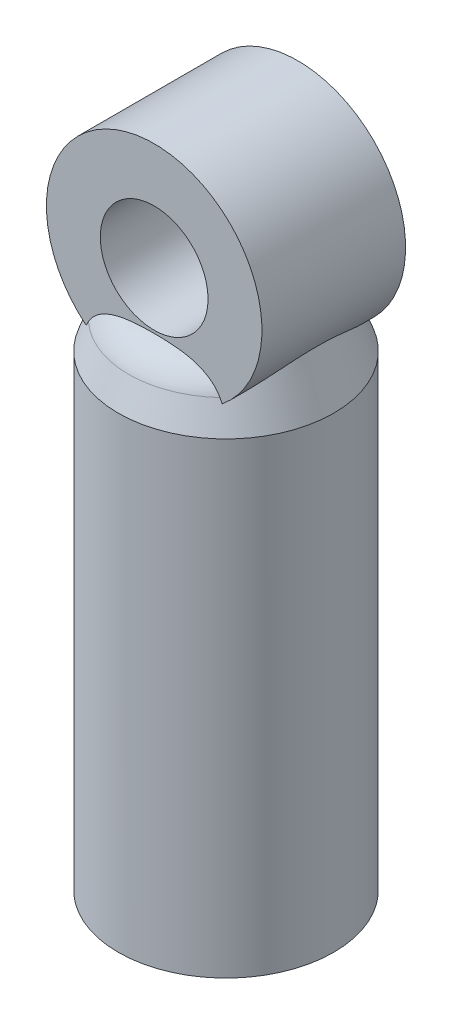
SolidWorks part; units mm, degrees
material "PLA"
ref_plane "Front Plane" through (0, 0, 0) normal (0, 0, 1) x (1, 0, 0)
ref_plane "Top Plane" through (0, 0, 0) normal (0, 1, 0) x (1, 0, 0)
ref_plane "Right Plane" through (0, 0, 0) normal (1, 0, 0) x (0, 0, -1)
sketch "Sketch1" plane through (0, 0, 0) normal (0, 1, 0) x (1, 0, 0)
  circle A0 centre (0, 0) radius 3
  circle A1 centre (0, 0) radius 1.5
  dimension "D1" = 6
  dimension "D2" = 3
extrude "Boss-Extrude1" add sketch "Sketch1" along normal blind 13
sketch "Sketch2" plane through (0, 0, 0) normal (0, 0, 1) x (1, 0, 0)
  line L0 (3, 13) -> (-3, 13) construction
  circle A0 centre (0, 16) radius 3
  circle A1 centre (0, 16) radius 1.5
  dimension "D1" = 6
  dimension "D2" = 3
extrude "Boss-Extrude2" add sketch "Sketch2" along normal mid plane 4 separate body
ref_plane "Plane1" through (0, 16, 0) normal (0, 1, 0) x (1, 0, 0)
sketch "Sketch3" plane through (0, 16, 0) normal (0, 1, 0) x (1, 0, 0)
  line L0 (-3, -2) -> (-3, 2)
  line L1 (-3, 2) -> (3, 2)
  line L2 (3, 2) -> (3, -2)
  line L3 (3, -2) -> (-3, -2)
sketch "Sketch4" plane through (0, 13, 0) normal (0, 1, 0) x (1, 0, 0)
  circle A1 centre (0, 0) radius 3
  circle A2 centre (0, 0) radius 3
  dimension "D1" = 0
extrude "Boss-Extrude3" add sketch "Sketch4" along normal blind 1.45 draft 20
fillet "Fillet1" radius 1 2 edges at (0, 14.45, -2.4722) (0, 14.45, 2.4722)
